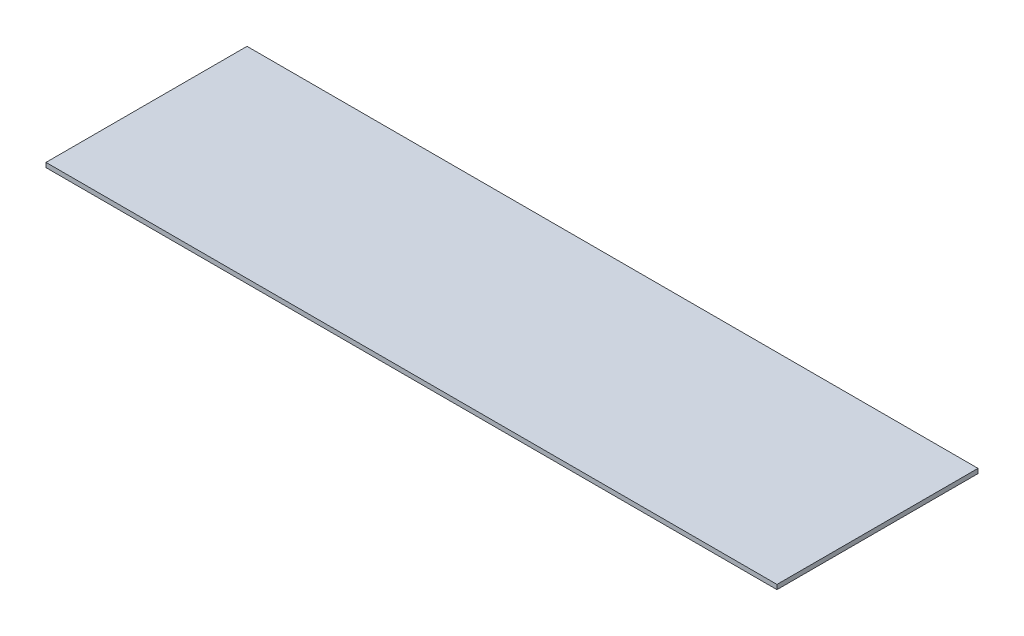
SolidWorks part; units mm, degrees
material "Lexan"
ref_plane "Front Plane" through (0, 0, 0) normal (0, 0, 1) x (1, 0, 0)
ref_plane "Top Plane" through (0, 0, 0) normal (0, 1, 0) x (1, 0, 0)
ref_plane "Right Plane" through (0, 0, 0) normal (1, 0, 0) x (0, 0, -1)
sketch "Sketch1" plane through (0, 0, 0) normal (0, 1, 0) x (1, 0, 0)
  line L1 (0, 0) -> (508, 0)
  line L2 (0, 0) -> (0, -139.7)
  line L3 (0, -139.7) -> (508, -139.7)
  line L4 (508, 0) -> (508, -139.7)
  dimension "D1" = 508
  dimension "D2" = 139.7
extrude "Boss-Extrude1" add sketch "Sketch1" along normal blind 3.175
